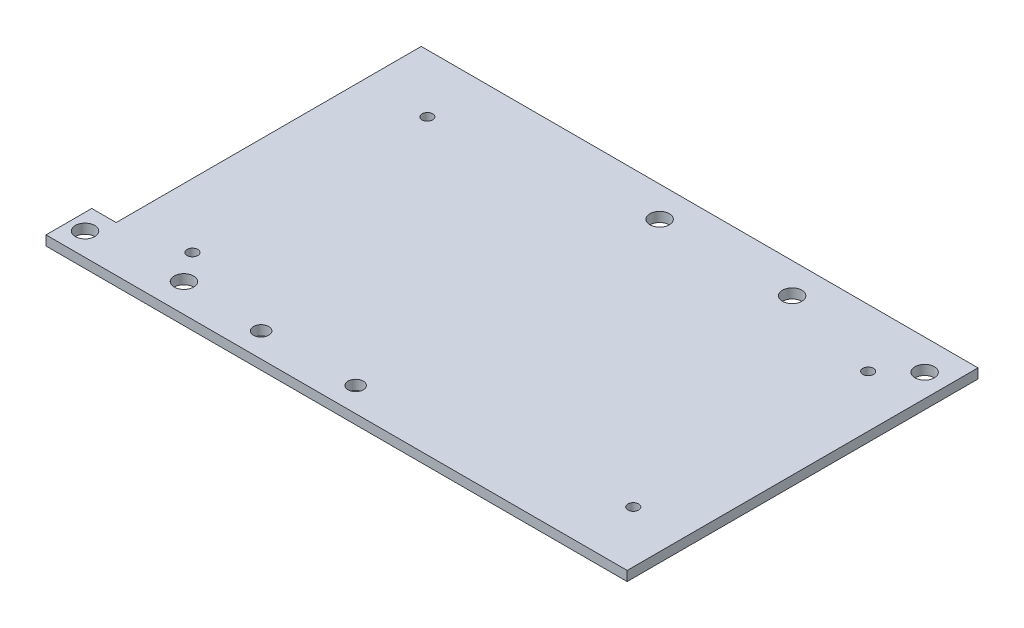
SolidWorks part; units mm, degrees
ref_plane "Front Plane" through (0, 0, 0) normal (0, 0, 1) x (1, 0, 0)
ref_plane "Top Plane" through (0, 0, 0) normal (0, 1, 0) x (1, 0, 0)
ref_plane "Right Plane" through (0, 0, 0) normal (1, 0, 0) x (0, 0, -1)
sketch "Sketch1" plane through (0, 0, 0) normal (0, 1, 0) x (1, 0, 0)
  line L0 (15, -15) -> (39.6804, -15) construction
  line L1 (0, 0) -> (365, 0)
  line L2 (0, 0) -> (0, -200)
  line L3 (-16, -230) -> (365, -230)
  line L4 (365, 0) -> (365, -230)
  line L5 (-5.3858, -215) -> (15.1434, -213.7531) construction
  line L6 (176.2667, -20) -> (263.1333, -20) construction
  line L8 (42, -38) -> (42, -192) construction
  line L9 (42, -192) -> (331, -192) construction
  line L10 (331, -192) -> (331, -38) construction
  line L11 (331, -38) -> (42, -38) construction
  line L12 (42, -38) -> (34, -38) construction
  line L13 (331, -38) -> (331, -30) construction
  line L14 (331, -192) -> (331, -200) construction
  line L15 (263.1333, -20) -> (350, -20) construction
  line L16 (176.2667, -20) -> (263.1333, -20) construction
  line L17 (0, -200) -> (-16, -200)
  line L18 (-16, -200) -> (-16, -230)
  line L19 (0, -200) -> (0, -230) construction
  line L20 (36.2332, -230) -> (35.123, -211.7222) construction
  line L22 (44.6629, -368.7873) -> (19.543, 44.788) construction
  line L23 (16.1302, -230) -> (15.1143, -213.2746) construction
  line L24 (-0.4861, 43.5714) -> (24.6338, -370.0038) construction
  line L25 (35.1725, -212.5366) -> (55.7016, -211.2896) construction
  line L26 (15.1434, -213.7531) -> (35.1725, -212.5366) construction
  circle A2 centre (-5.3858, -215) radius 6.35
  circle A3 centre (55.7016, -211.2896) radius 6.35
  circle A8 centre (42, -38) radius 3.5
  circle A9 centre (42, -192) radius 3.5
  circle A10 centre (331, -192) radius 3.5
  circle A11 centre (331, -38) radius 3.5
  circle A12 centre (263.1333, -20) radius 6.35
  circle A13 centre (171, -214) radius 5
  circle A17 centre (109, -214) radius 5
  circle A19 centre (176.2667, -20) radius 6.35
  circle A20 centre (350, -20) radius 6.35
  circle A21 centre (176.2667, -20) radius 6.35 construction
  circle A22 centre (350, -20) radius 6.35 construction
  circle A23 centre (176.2667, -20) radius 6.35 construction
  circle A24 centre (350, -20) radius 6.35 construction
  point P10 (331, -115)
  point P11 (365, -115)
  point P33 (137.9099, -221.2896)
  point P37 (0, 0)
  dimension "D10" = 7
  dimension "D19" = 12.7
  dimension "D21" = 10
  dimension "D2" = 365
  dimension "D3" = 15
  dimension "D4" = 15
  dimension "D5" = 15
  dimension "D6" = 61.2
  dimension "D7" = 230
  dimension "D8" = 15
  dimension "D9" = 20
  dimension "D11" = 289
  dimension "D12" = 154
  dimension "D13" = 8
  dimension "D14" = 34
  dimension "D15" = 8
  dimension "D16" = 16
  dimension "D17" = 8
  dimension "D18" = 30
  dimension "D20" = 194
  dimension "D22" = 62
  dimension "D23" = 16
extrude "Boss-Extrude1" add sketch "Sketch1" against normal blind 6.35
